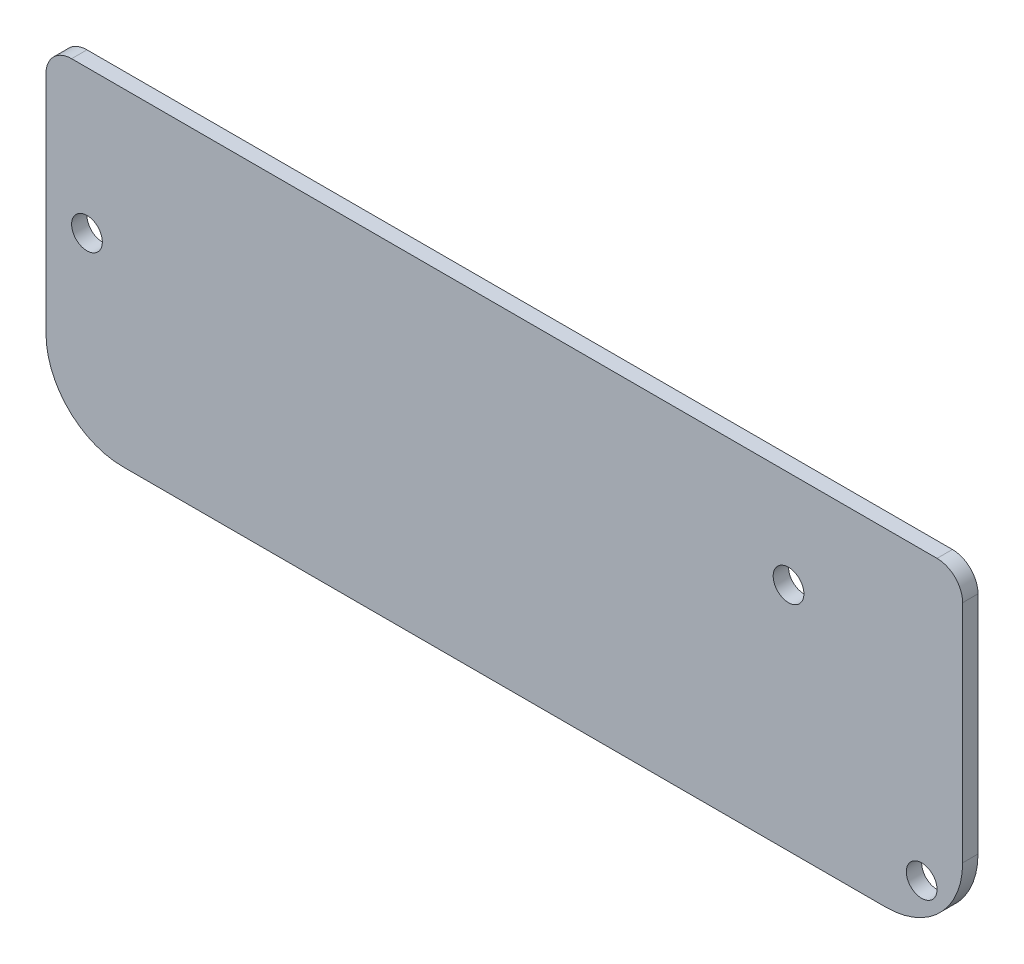
SolidWorks part; units mm, degrees
ref_plane "Plan de face" through (0, 0, 0) normal (0, 0, 1) x (1, 0, 0)
ref_plane "Plan de dessus" through (0, 0, 0) normal (0, 1, 0) x (1, 0, 0)
ref_plane "Plan de droite" through (0, 0, 0) normal (1, 0, 0) x (0, 0, -1)
sketch "Esquisse1" plane through (0, 0, 0) normal (0, 0, 1) x (1, 0, 0)
  line L1 (118.1017, 78.6323) -> (267.1017, 78.6323)
  line L2 (103.1017, 93.6323) -> (103.1017, 137.6323)
  line L3 (108.1017, 142.6323) -> (277.1017, 142.6323)
  line L4 (282.1017, 93.6323) -> (282.1017, 137.6323)
  arc A0 (277.1017, 142.6323) -> (282.1017, 137.6323) centre (277.1017, 137.6323) cw
  arc A1 (103.1017, 137.6323) -> (108.1017, 142.6323) centre (108.1017, 137.6323) cw
  arc A2 (267.1017, 78.6323) -> (282.1017, 93.6323) centre (267.1017, 93.6323) ccw
  arc A3 (118.1017, 78.6323) -> (103.1017, 93.6323) centre (118.1017, 93.6323) cw
  point P6 (282.1017, 142.6323)
  point P9 (103.1017, 142.6323)
  point P12 (282.1017, 78.6323)
  dimension "D3" = 5
  dimension "D4" = 15
  dimension "D1" = 179
  dimension "D2" = 64
extrude "Boss.-Extru.1" add sketch "Esquisse1" along normal blind 3
sketch "Esquisse2" plane through (0, 0, 0) normal (0, 0, -1) x (-1, 0, 0)
  line L0 (-103.1017, 137.6323) -> (-103.1017, 93.6323) construction
  line L1 (-118.1017, 78.6323) -> (-267.1017, 78.6323) construction
  line L2 (-282.1017, 93.6323) -> (-282.1017, 137.6323) construction
  line L3 (-277.1017, 142.6323) -> (-108.1017, 142.6323) construction
  circle A0 centre (-111.1017, 114.6323) radius 3
  circle A1 centre (-111.1017, 86.6323) radius 3
  circle A2 centre (-248.1017, 123.6323) radius 3
  circle A3 centre (-274.1017, 86.6323) radius 3
  dimension "D1" = 8
  dimension "D2" = 8
  dimension "D3" = 8
  dimension "D4" = 8
  dimension "D5" = 19
  dimension "D6" = 34
  dimension "D7" = 8
  dimension "D8" = 28
extrude "Enlèv. mat.-Extru.1" cut sketch "Esquisse2" against normal blind 3 contours A0 | A2 | A3
